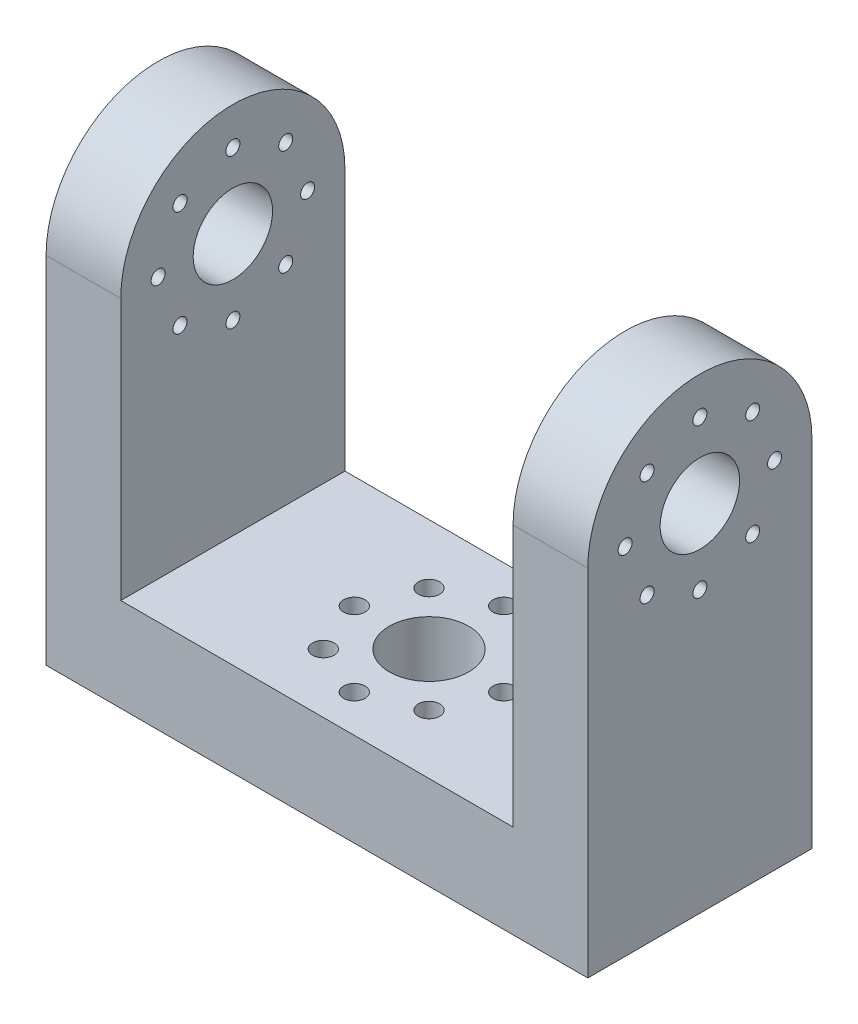
SolidWorks part; units mm, degrees
note: The reader was unsure of these and kept them because the rebuilt part matched: shared geometry of "Szkic3<3>".
material "ABS"
ref_plane "Płaszczyzna przednia" through (0, 0, 0) normal (0, 0, 1) x (1, 0, 0)
ref_plane "Płaszczyzna górna" through (0, 0, 0) normal (0, 1, 0) x (1, 0, 0)
ref_plane "Płaszczyzna prawa" through (0, 0, 0) normal (1, 0, 0) x (0, 0, -1)
sketch "Szkic1" plane through (0, 0, 0) normal (0, 0, 1) x (1, 0, 0)
  line L0 (0, 0) -> (0, 50) construction
  line L1 (21, 10) -> (-21, 10)
  line L2 (-21, 10) -> (-21, 50)
  line L3 (-21, 50) -> (-29, 50)
  line L4 (-29, 50) -> (-29, 0)
  line L5 (-29, 0) -> (29, 0)
  line L6 (29, 50) -> (21, 50)
  line L7 (29, 50) -> (29, 0)
  line L8 (21, 10) -> (21, 50)
  point P12 (0, 10)
  dimension "D1" = 8
  dimension "D2" = 10
  dimension "D3" = 21
  dimension "D4" = 40
extrude "Dodanie-wyciągnięcie1" add sketch "Szkic1" along normal blind 24
sketch "Szkic2" plane through (29, 0, 0) normal (1, 0, 0) x (0, 0, -1)
  line L0 (0, 10.0851) -> (-24, 10.0851)
  line L1 (0, 0) -> (0, 50) construction
  line L2 (-24, 0) -> (-24, 50) construction
  line L3 (-24, 50) -> (0, 50) construction
  line L4 (0, 38) -> (0, 10.0851)
  line L5 (-24, 0) -> (-24, 50) construction
  line L6 (-24, 38) -> (-24, 10.0851)
  line L7 (-24, 0) -> (-24, 11.5166)
  circle A0 centre (-12, 38) radius 4.25
  arc A1 (0, 38) -> (-16.0342, 49.3016) centre (-12, 38) ccw
  circle A2 centre (-12, 38) radius 12
  dimension "D1" = 24
  dimension "D2" = 8.5
extrude "Wytnij-wyciągnięcie1" cut sketch "Szkic2" against normal through all
sketch "Szkic3" plane through (0, 10, 0) normal (0, 1, 0) x (1, 0, 0)
  line L0 (0, 0) -> (0, -6.721) construction
  circle B0 centre (0, -12) radius 4.25
  circle B1 centre (5.6569, -17.6569) radius 0.65
  circle B2 centre (8, -12) radius 0.65
  circle B3 centre (0, -20) radius 0.65
  circle B4 centre (-5.6569, -17.6569) radius 0.65
  circle B5 centre (-8, -12) radius 0.65
  circle B6 centre (-5.6569, -6.3431) radius 0.65
  circle B7 centre (0, -4) radius 0.65
  circle B8 centre (5.6569, -6.3431) radius 0.65
  circle B9 centre (8, -12) radius 1.15
  circle B10 centre (8, -12) radius 0.15
  circle B11 centre (5.6569, -17.6569) radius 1.15
  circle B12 centre (0, -20) radius 1.15
  circle B13 centre (-5.6569, -17.6569) radius 1.15
  circle B14 centre (-8, -12) radius 1.15
  circle B15 centre (-5.6569, -6.3431) radius 1.15
  circle B16 centre (0, -4) radius 1.15
  circle B17 centre (5.6569, -6.3431) radius 1.15
sketch_block_instance "Blok1-1"
sketch_block "Blok1" parameters "D1"=8.5
extrude "Wytnij-wyciągnięcie2" cut sketch "Szkic3" against normal through all
sketch "Szkic4" plane through (-29, 0, 0) normal (-1, 0, 0) x (0, 0, 1)
  line L0 (12, 38) -> (-10.5554, 38) construction
  circle A0 centre (4, 38) radius 0.75
  circle A1 centre (12, 46) radius 0.75
  circle A2 centre (20, 38) radius 0.75
  circle A3 centre (12, 30) radius 0.75
  circle A4 centre (6.3431, 32.3431) radius 0.75
  circle A5 centre (4, 38) radius 0.75
  circle A6 centre (6.3431, 43.6569) radius 0.75
  circle A7 centre (12, 46) radius 0.75
  circle A8 centre (17.6569, 43.6569) radius 0.75
  circle A9 centre (20, 38) radius 0.75
  circle A10 centre (17.6569, 32.3431) radius 0.75
  point P2 (12, 38)
  point P15 (12, 38)
  point P29 (12, 38)
  dimension "D1" = 8
  dimension "D3" = 1.5
  dimension "D4" = 8
  dimension "D2" = 4
extrude "Wytnij-wyciągnięcie3" cut sketch "Szkic4" against normal through all contours A1 | A8 | L0 A0 | A5 L0 | A4 | A10 | A2 | A3 | A6
extrude "Wytnij-wyciągnięcie4" cut sketch "Szkic3<3>" against normal blind 4
sketch "Szkic3<3>" plane through (0, 10, 0) normal (0, 1, 0) x (1, 0, 0) same geometry as "Szkic3"
